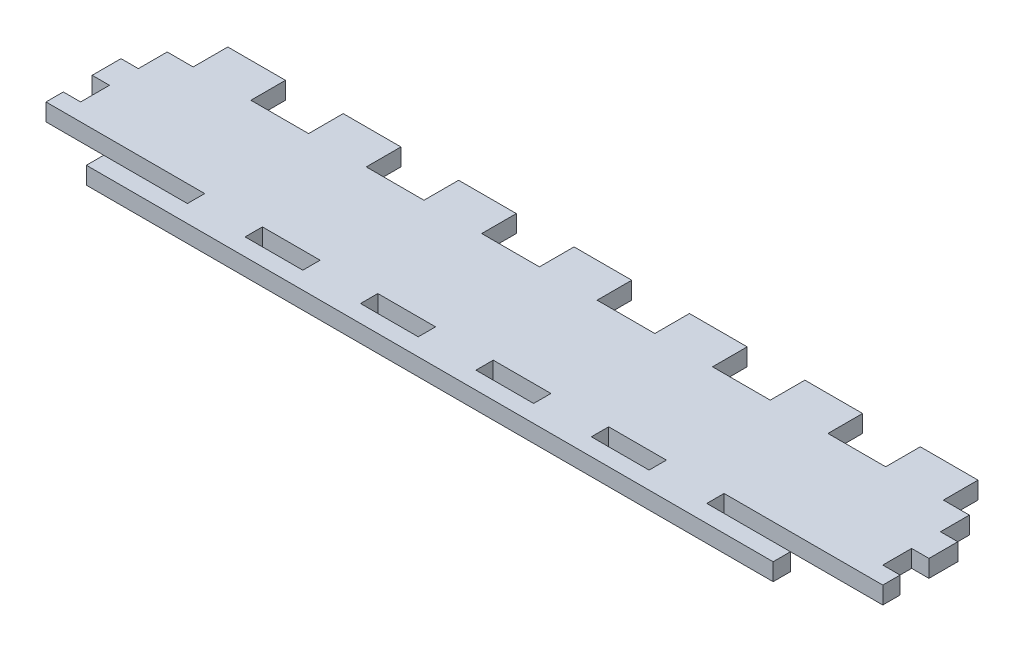
SolidWorks part; units mm, degrees
material "Maple"
ref_plane "Front Plane" through (0, 0, 0) normal (0, 0, 1) x (1, 0, 0)
ref_plane "Top Plane" through (0, 0, 0) normal (0, 1, 0) x (1, 0, 0)
ref_plane "Right Plane" through (0, 0, 0) normal (1, 0, 0) x (0, 0, -1)
sketch "Sketch1" plane through (0, 0, 0) normal (0, 1, 0) x (1, 0, 0)
  line L1 (0, 0) -> (145, 0)
  line L2 (0, 0) -> (0, -18)
  line L3 (0, -18) -> (145, -18)
  line L4 (145, 0) -> (145, -18)
  dimension "D1" = 145
  dimension "D2" = 18
extrude "Boss-Extrude1" add sketch "Sketch1" along normal blind 3
sketch "Sketch2" plane through (0, 0, 0) normal (0, -1, 0) x (1, 0, 0)
  line L0 (72.5, 18) -> (72.5, 0) construction
  line L1 (0, 18) -> (145, 18) construction
  line L2 (145, 0) -> (0, 0) construction
  line L4 (67.5, 21) -> (77.5, 21)
  line L5 (67.5, 21) -> (67.5, 18)
  line L6 (67.5, 18) -> (77.5, 18)
  line L7 (77.5, 21) -> (77.5, 18)
  line L8 (67.5, 21) -> (77.5, 18) construction
  line L9 (67.5, 18) -> (77.5, 21) construction
  line L10 (67.5, 0) -> (77.5, 0)
  line L11 (67.5, 0) -> (67.5, -6)
  line L12 (67.5, -6) -> (77.5, -6)
  line L13 (77.5, 0) -> (77.5, -6)
  line L14 (67.5, 0) -> (77.5, -6) construction
  line L15 (67.5, -6) -> (77.5, 0) construction
  point P6 (72.5, 19.5)
  point P11 (72.5, -3)
  point P16 (77.5, -14.7613)
  dimension "D1" = 10
  dimension "D2" = 3
  dimension "D3" = 6
extrude "Boss-Extrude2" add sketch "Sketch2" against normal through all
pattern_linear "LPattern1" count 4 spacing 20 along (1, 0, 0) count 4 spacing 20 along (-1, 0, 0) of "Boss-Extrude2" pattern seed only yes
sketch "Sketch3" plane through (0, 3, 0) normal (0, 1, 0) x (1, 0, 0)
  line L0 (57.5, -21) -> (47.5, -21) construction
  line L1 (0, -21) -> (145, -21)
  line L2 (0, -21) -> (0, -24)
  line L3 (0, -24) -> (145, -24)
  line L4 (145, -21) -> (145, -24)
  line L5 (0, 0) -> (0, -18) construction
  line L6 (145, -18) -> (145, 0) construction
  dimension "D1" = 3
extrude "Boss-Extrude3" add sketch "Sketch3" against normal through all
sketch "Sketch4" plane through (0, 3, 0) normal (0, 1, 0) x (1, 0, 0)
  line L9 (7.5, -18) -> (17.5, -18)
  line L10 (7.5, -18) -> (7.5, -21)
  line L11 (7.5, -21) -> (17.5, -21)
  line L12 (17.5, -18) -> (17.5, -21)
  line L13 (137.5, -18) -> (127.5, -18)
  line L14 (137.5, -18) -> (137.5, -21)
  line L15 (137.5, -21) -> (127.5, -21)
  line L16 (127.5, -18) -> (127.5, -21)
extrude "Cut-Extrude1" cut sketch "Sketch4" against normal through all
sketch "Sketch5" plane through (0, 3, 0) normal (0, 1, 0) x (1, 0, 0)
  line L0 (27.5, -21) -> (0, -21) construction
  line L1 (0, -24) -> (13, -24)
  line L2 (0, -24) -> (0, -21)
  line L3 (0, -21) -> (13, -21)
  line L4 (13, -24) -> (13, -21)
  line L5 (145, -21) -> (117.5, -21) construction
  line L6 (145, -24) -> (132, -24)
  line L7 (145, -24) -> (145, -21)
  line L8 (145, -21) -> (132, -21)
  line L9 (132, -24) -> (132, -21)
  dimension "D1" = 13
extrude "Cut-Extrude2" cut sketch "Sketch5" against normal through all
sketch "Sketch6" plane through (0, 0, 0) normal (0, -1, 0) x (1, 0, 0)
  line L0 (0, 0) -> (0, 18) construction
  line L1 (3, 15) -> (0, 15)
  line L2 (3, 15) -> (3, 10)
  line L3 (3, 10) -> (0, 10)
  line L4 (0, 15) -> (0, 10)
  line L5 (7.5, 0) -> (0, 0) construction
  line L6 (3, 5) -> (0, 5)
  line L7 (3, 5) -> (3, 0)
  line L8 (3, 0) -> (0, 0)
  line L9 (0, 5) -> (0, 0)
  line L10 (145, 18) -> (145, 0) construction
  line L11 (142, 15) -> (145, 15)
  line L12 (142, 15) -> (142, 10)
  line L13 (142, 10) -> (145, 10)
  line L14 (145, 15) -> (145, 10)
  line L15 (145, 0) -> (137.5, 0) construction
  line L16 (142, 5) -> (145, 5)
  line L17 (142, 5) -> (142, 0)
  line L18 (142, 0) -> (145, 0)
  line L19 (145, 5) -> (145, 0)
extrude "Cut-Extrude3" cut sketch "Sketch6" against normal through all
